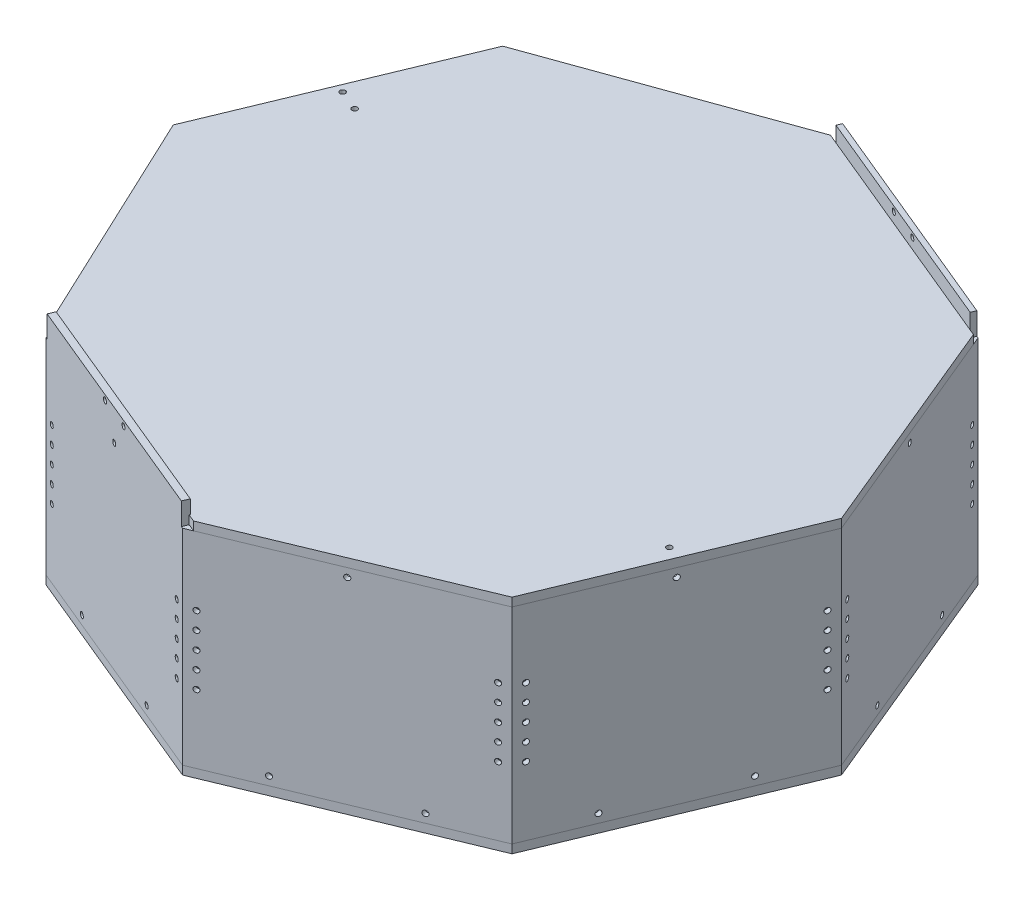
SolidWorks part; units mm, degrees
material "PMMA"
ref_plane "前视基准面" through (0, 0, 0) normal (0, 0, 1) x (1, 0, 0)
ref_plane "上视基准面" through (0, 0, 0) normal (0, 1, 0) x (1, 0, 0)
ref_plane "右视基准面" through (0, 0, 0) normal (1, 0, 0) x (0, 0, -1)
sketch "草图1" plane through (0, 0, 0) normal (0, 1, 0) x (1, 0, 0)
  line L0 (0, 0) -> (189.4186, 0) construction
  line L1 (189.4186, 0) -> (133.9392, 133.9392)
  line L2 (133.9392, 133.9392) -> (0, 189.4186)
  line L3 (0, 189.4186) -> (-133.9392, 133.9392)
  line L4 (-133.9392, 133.9392) -> (-189.4186, 0)
  line L5 (-189.4186, 0) -> (-133.9392, -133.9392)
  line L6 (-133.9392, -133.9392) -> (0, -189.4186)
  line L7 (0, -189.4186) -> (133.9392, -133.9392)
  line L8 (133.9392, -133.9392) -> (189.4186, 0)
  line L9 (0, -192.6658) -> (136.2353, -136.2353)
  line L10 (136.2353, -136.2353) -> (192.6658, 0)
  line L11 (192.6658, 0) -> (136.2353, 136.2353)
  line L12 (136.2353, 136.2353) -> (0, 192.6658)
  line L13 (0, 192.6658) -> (-136.2353, 136.2353)
  line L14 (-136.2353, 136.2353) -> (-192.6658, 0)
  line L15 (-192.6658, 0) -> (-136.2353, -136.2353)
  line L16 (-136.2353, -136.2353) -> (0, -192.6658)
  circle A2 centre (0, 0) radius 175 construction
  dimension "D1" = 3
  dimension "D3" = 350
extrude "凸台-拉伸1" add sketch "草图1" along normal blind 120
sketch "草图2" plane through (0, 0, 0) normal (0, -1, 0) x (1, 0, 0)
  line L10 (0, 192.6658) -> (-136.2353, 136.2353)
  line L11 (-136.2353, 136.2353) -> (-192.6658, 0)
  line L12 (-192.6658, 0) -> (-136.2353, -136.2353)
  line L13 (-136.2353, -136.2353) -> (0, -192.6658)
  line L14 (0, -192.6658) -> (136.2353, -136.2353)
  line L15 (136.2353, -136.2353) -> (192.6658, 0)
  line L16 (192.6658, 0) -> (136.2353, 136.2353)
  line L17 (136.2353, 136.2353) -> (0, 192.6658)
  line L18 (0, 192.6658) -> (-136.2353, 136.2353)
  line L19 (-136.2353, 136.2353) -> (-192.6658, 0)
  line L20 (-192.6658, 0) -> (-136.2353, -136.2353)
  line L21 (-136.2353, -136.2353) -> (0, -192.6658)
  line L22 (0, -192.6658) -> (136.2353, -136.2353)
  line L23 (136.2353, -136.2353) -> (192.6658, 0)
  line L24 (192.6658, 0) -> (136.2353, 136.2353)
  line L25 (136.2353, 136.2353) -> (0, 192.6658)
  dimension "D1" = 0
extrude "凸台-拉伸2" add sketch "草图2" along normal blind 5 separate body
sketch "草图3" plane through (0, -5, 0) normal (0, -1, 0) x (1, 0, 0)
  circle A0 centre (0, 0) radius 165 construction
  circle A1 centre (0, -165) radius 5.2
  circle A2 centre (-116.6726, -116.6726) radius 5.2
  circle A3 centre (-165, 0) radius 5.2
  circle A4 centre (-116.6726, 116.6726) radius 5.2
  circle A5 centre (0, 165) radius 5.2
  circle A6 centre (116.6726, 116.6726) radius 5.2
  circle A7 centre (165, 0) radius 5.2
  circle A8 centre (116.6726, -116.6726) radius 5.2
  circle A10 centre (0, 0) radius 22.5
  circle A11 centre (0, 0) radius 29 construction
  circle A12 centre (29, 0) radius 2.05
  circle A13 centre (-14.5, -25.1147) radius 2.05
  circle A14 centre (-14.5, 25.1147) radius 2.05
  dimension "D1" = 330
  dimension "D2" = 10.4
  dimension "D4" = 45
  dimension "D5" = 58
  dimension "D6" = 4.1
  dimension "D3" = 8
  dimension "D7" = 3
extrude "切除-拉伸1" cut sketch "草图3" against normal through all
sketch "草图6" plane through (0, -5, 0) normal (0, -1, 0) x (1, 0, 0)
  line L0 (0, 189.4186) -> (133.9392, 133.9392) construction
  line L1 (0, 189.4186) -> (133.9392, 133.9392) construction
  line L2 (66.9696, 161.6789) -> (0, 0) construction
  line L3 (-32.7204, 170.4534) -> (0, 0) construction
  line L4 (0, 0) -> (-97.392, 143.6656) construction
  line L5 (-97.392, 143.6656) -> (-32.7204, 170.4534) construction
  line L6 (-65.0562, 157.0595) -> (0, 0) construction
  line L7 (32.7204, 170.4534) -> (97.392, 143.6656) construction
  line L8 (65.0562, 157.0595) -> (0, 0) construction
  circle A11 centre (32.7204, 170.4534) radius 1.6
  circle A12 centre (97.392, 143.6656) radius 1.6
  circle A13 centre (143.6656, 97.392) radius 1.6
  circle A14 centre (170.4534, 32.7204) radius 1.6
  circle A15 centre (170.4534, -32.7204) radius 1.6
  circle A16 centre (143.6656, -97.392) radius 1.6
  circle A17 centre (97.392, -143.6656) radius 1.6
  circle A18 centre (32.7204, -170.4534) radius 1.6
  circle A19 centre (-32.7204, -170.4534) radius 1.6
  circle A20 centre (-97.392, -143.6656) radius 1.6
  circle A21 centre (-143.6656, -97.392) radius 1.6
  circle A22 centre (-170.4534, -32.7204) radius 1.6
  circle A23 centre (-170.4534, 32.7204) radius 1.6
  circle A24 centre (-143.6656, 97.392) radius 1.6
  circle A25 centre (-97.392, 143.6656) radius 1.6
  circle A26 centre (-32.7204, 170.4534) radius 1.6
  dimension "D1" = 3.2
  dimension "D2" = 35
  dimension "D3" = 5
  dimension "D4" = 170
extrude "切除-拉伸2" cut sketch "草图6" against normal through all
sketch "草图4" plane through (0, 120, 0) normal (0, 1, 0) x (1, 0, 0)
  line L0 (-133.9392, -133.9392) -> (0, -189.4186) construction
  line L1 (133.9392, 133.9392) -> (0, 189.4186) construction
  line L2 (-133.9392, -133.9392) -> (0, -189.4186) construction
  line L3 (133.9392, 133.9392) -> (0, 189.4186) construction
  line L4 (4.573, -190.7716) -> (-138.1295, -131.6623)
  line L5 (138.1295, 131.6623) -> (-4.573, 190.7716)
  line L6 (164.4506, -68.1177) -> (-164.4506, 68.1177) construction
  line L7 (0, 0) -> (-18.7005, -45.1469) construction
  line L8 (-136.2353, -136.2353) -> (0, -192.6658)
  line L9 (0, -192.6658) -> (136.2353, -136.2353)
  line L10 (136.2353, -136.2353) -> (192.6658, 0)
  line L11 (192.6658, 0) -> (136.2353, 136.2353)
  line L12 (136.2353, 136.2353) -> (0, 192.6658)
  line L13 (0, 192.6658) -> (-136.2353, 136.2353)
  line L14 (-136.2353, 136.2353) -> (-192.6658, 0)
  line L15 (-192.6658, 0) -> (-136.2353, -136.2353)
  line L17 (4.573, -190.7716) -> (136.2353, -136.2353)
  line L18 (136.2353, -136.2353) -> (192.6658, 0)
  line L19 (192.6658, 0) -> (138.1295, 131.6623)
  line L21 (-4.573, 190.7716) -> (-136.2353, 136.2353) construction
  line L22 (-136.2353, 136.2353) -> (-192.6658, 0) construction
  line L23 (-192.6658, 0) -> (-138.1295, -131.6623) construction
  line L24 (-133.9392, 133.9392) -> (-189.4186, 0) construction
  line L25 (-136.2353, 136.2353) -> (-145.4741, 140.0621) construction
  line L26 (-145.4741, 140.0621) -> (-201.9046, 3.8268)
  line L27 (-201.9046, 3.8268) -> (-192.6658, 0) construction
  line L28 (-4.573, 190.7716) -> (-145.4741, 140.0621)
  line L29 (-201.9046, 3.8268) -> (-138.1295, -131.6623)
  circle A0 centre (157.0595, -65.0562) radius 1.6
  circle A1 centre (-157.0595, 65.0562) radius 1.6
  circle A2 centre (-169.07, 70.0311) radius 1.6
  dimension "D4" = 3.2
  dimension "D2" = 0.5
  dimension "D3" = 0.5
  dimension "D5" = 5
  dimension "D6" = 10
  dimension "D7" = 5
  dimension "D1" = 0
extrude "凸台-拉伸3" add sketch "草图4" along normal blind 5 separate body
sketch "草图8" plane through (-68.1177, 0, 164.4506) normal (-0.3827, 0, 0.9239) x (0.9239, 0, 0.3827)
  line L1 (-72.4874, 120) -> (72.4874, 120)
  line L2 (-72.4874, 120) -> (-72.4874, 133)
  line L3 (-72.4874, 133) -> (72.4874, 133)
  line L4 (72.4874, 120) -> (72.4874, 133)
  line L5 (0, 133) -> (0, 120) construction
  line L6 (-10, 130) -> (10, 130) construction
  circle A1 centre (-10, 130) radius 1.6
  circle A2 centre (10, 130) radius 1.6
  dimension "D2" = 3.2
  dimension "D1" = 13
  dimension "D3" = 20
  dimension "D4" = 3
extrude "凸台-拉伸4" add sketch "草图8" against normal blind 4
extrude "凸台-拉伸6" add sketch "草图8<2>" against normal up to surface (356 mm away) from surface up to face at (68.1177, 60, -164.4506) starting at face at (66.9696, 60, -161.6789)
sketch "草图8<2>" plane through (-68.1177, 0, 164.4506) normal (-0.3827, 0, 0.9239) x (0.9239, 0, 0.3827) same geometry as "草图8"
sketch "草图9" plane through (-164.4506, 0, -68.1177) normal (-0.9239, 0, -0.3827) x (-0.3827, 0, 0.9239)
  line L0 (-35, 5) -> (35, 5) construction
  line L1 (0, 5) -> (0, 0) construction
  line L2 (73.73, 0) -> (-73.73, 0) construction
  line L3 (-73.73, 60) -> (73.73, 60) construction
  line L4 (-73.73, 120) -> (-73.73, 0) construction
  line L5 (73.73, 120) -> (73.73, 0) construction
  line L6 (-73.73, 120) -> (73.73, 120) construction
  line L7 (-67.4874, 80) -> (-67.4874, 40) construction
  line L8 (67.4874, 70) -> (67.4874, 50) construction
  circle A0 centre (-35, 5) radius 1.6
  circle A1 centre (35, 5) radius 1.6
  circle A4 centre (0, 115) radius 1.6
  circle A5 centre (-67.4874, 80) radius 1.6
  circle A6 centre (-67.4874, 40) radius 1.6
  circle A9 centre (67.4874, 70) radius 1.6
  circle A10 centre (67.4874, 50) radius 1.6
  circle A11 centre (-67.4874, 60) radius 1.6
  dimension "D2" = 3.2
  dimension "D4" = 3.2
  dimension "D6" = 3.2
  dimension "D1" = 5
  dimension "D3" = 70
  dimension "D5" = 40
  dimension "D7" = 5
  dimension "D8" = 5
  dimension "D9" = 5
  dimension "D10" = 20
extrude "切除-拉伸5" cut sketch "草图9" against normal through all both and the other way through all
pattern_circular "阵列(圆周)2" count 8 over 360 about axis through (0, 0, 0) along (0, -1, 0) of "切除-拉伸5"
sketch "草图10" plane through (0, 0, 0) normal (0, 1, 0) x (1, 0, 0)
  line L0 (133.9392, 133.9392) -> (123.9148, 138.0914)
  line L1 (133.9392, 133.9392) -> (0, 189.4186) construction
  line L2 (121.7352, 134.8295) -> (134.8295, 121.7352)
  line L3 (189.4186, 0) -> (133.9392, 133.9392) construction
  line L4 (138.0914, 123.9148) -> (133.9392, 133.9392)
  arc A0 (134.8295, 121.7352) -> (138.0914, 123.9148) centre (136.2437, 123.1494) ccw
  arc A1 (123.9148, 138.0914) -> (121.7352, 134.8295) centre (123.1494, 136.2437) ccw
  point P10 (141.9392, 114.6255)
  point P13 (114.6255, 141.9392)
  dimension "D2" = 2
  dimension "D1" = 8
extrude "凸台-拉伸5" add sketch "草图10" along normal blind 60 from offset 30 separate body
sketch "草图11" plane through (66.9696, 0, -161.6789) normal (0.3827, 0, -0.9239) x (-0.9239, 0, -0.3827)
  circle A10 centre (-67.4874, 80) radius 1.2
  circle A11 centre (-67.4874, 70) radius 1.2
  circle A12 centre (-67.4874, 60) radius 1.2
  circle A13 centre (-67.4874, 50) radius 1.2
  circle A14 centre (-67.4874, 40) radius 1.2
  dimension "D1" = 2.4
extrude "切除-拉伸6" cut sketch "草图11" against normal up to surface (6.091 mm away) up to face at (128.2823, 60, -128.2823)
sketch "草图13" plane through (161.6789, 0, -66.9696) normal (0.9239, 0, -0.3827) x (-0.3827, 0, -0.9239)
  circle A0 centre (67.4874, 80) radius 1.2
  circle A1 centre (67.4874, 70) radius 1.2
  circle A2 centre (67.4874, 60) radius 1.2
  circle A3 centre (67.4874, 50) radius 1.2
  circle A4 centre (67.4874, 40) radius 1.2
  dimension "D1" = 2.4
extrude "切除-拉伸7" cut sketch "草图13" against normal up to surface (7.0851 mm away) up to face at (125.8802, 80, -130.6845)
pattern_circular "阵列(圆周)3" count 8 over 360 about axis through (0, 0, 0) along (0, -1, 0) of bodies 122
sketch "草图14" plane through (0, -5, 0) normal (0, -1, 0) x (1, 0, 0)
  line L1 (50, -50) -> (-50, -50) construction
  line L2 (50, -50) -> (50, 50) construction
  line L3 (50, 50) -> (-50, 50) construction
  line L4 (-50, -50) -> (-50, 50) construction
  line L5 (50, -50) -> (-50, 50) construction
  line L6 (50, 50) -> (-50, -50) construction
  line L14 (54, -54) -> (54, 54) construction
  line L15 (54, 54) -> (-54, 54) construction
  line L16 (-54, -54) -> (-54, 54) construction
  line L17 (54, -54) -> (-54, -54) construction
  line L19 (-50, -50) -> (-54, -50)
  line L20 (-50, -50) -> (-50, 50)
  line L21 (-50, 50) -> (-54, 50)
  line L22 (-54, -50) -> (-54, 50)
  point P0 (0, 0)
  dimension "D1" = 100
  dimension "D2" = 4
extrude "凸台-拉伸7" add sketch "草图14" along normal blind 55 separate body
sketch "草图15" plane through (0, -60, 0) normal (0, -1, 0) x (1, 0, 0)
  line L0 (-50, 50) -> (-54, 50) construction
  line L1 (-50, -50) -> (50, -50)
  line L2 (-50, -50) -> (-50, 50)
  line L3 (-50, 50) -> (50, 50)
  line L4 (50, -50) -> (50, 50)
  line L5 (-50, -50) -> (-50, 50) construction
  line L6 (-54, -50) -> (-50, -50) construction
  point P9 (-50, -47.3887)
  dimension "D1" = 100
extrude "凸台-拉伸8" add sketch "草图15" along normal blind 3 separate body
sketch "草图16" plane through (0, -63, 0) normal (0, -1, 0) x (1, 0, 0)
  line L0 (50, 0) -> (-50, 0) construction
  line L1 (50, -50) -> (50, 50) construction
  line L2 (-50, 50) -> (-50, -50) construction
  circle A0 centre (0, 0) radius 3.05
  circle A1 centre (0, 0) radius 12.5 construction
  circle A2 centre (0, -12.5) radius 1.35
  circle A3 centre (-10.8253, 6.25) radius 1.35
  circle A4 centre (10.8253, 6.25) radius 1.35
  point P12 (10.826, 6.2489)
  point P13 (-10.7914, 6.3084)
  dimension "D1" = 6.1
  dimension "D2" = 25
  dimension "D3" = 2.7
  dimension "D4" = 3
extrude "切除-拉伸8" cut sketch "草图16" against normal up to next (3 mm away)
sketch "草图17" plane through (0, -5, 0) normal (0, -1, 0) x (1, 0, 0)
  line L0 (-59, -49.5402) -> (-59, 46.5588) construction
  line L1 (-50, -50) -> (-50, 50) construction
  line L2 (-50, 50) -> (-54, 50) construction
  line L3 (-54, -50) -> (-50, -50) construction
  line L4 (-54, 50) -> (-54, -50) construction
  circle A0 centre (-59, -30) radius 1.6
  circle A1 centre (-59, 30) radius 1.6
  circle A2 centre (-30, 59) radius 1.6
  circle A3 centre (30, 59) radius 1.6
  circle A4 centre (59, 30) radius 1.6
  circle A5 centre (59, -30) radius 1.6
  circle A6 centre (30, -59) radius 1.6
  circle A7 centre (-30, -59) radius 1.6
  circle A8 centre (0, 0) radius 66.1891 construction
  point P16 (-29.8667, -59.0676)
  point P29 (30.0482, -58.9755)
  dimension "D2" = 3.2
  dimension "D1" = 5
  dimension "D3" = 20
  dimension "D4" = 20
  dimension "D5" = 4
extrude "切除-拉伸9" cut sketch "草图17" against normal up to next (5 mm away)
sketch "草图18" plane through (-54, 0, 0) normal (-1, 0, 0) x (0, 0, 1)
  line L0 (-50, -10) -> (50, -10) construction
  line L1 (-50, -60) -> (-50, -5) construction
  line L2 (50, -60) -> (50, -5) construction
  line L3 (50, -5) -> (-50, -5) construction
  line L4 (-50, -32.5) -> (-36.0118, -32.5) construction
  circle A0 centre (-30, -10) radius 1.6
  circle A1 centre (30, -10) radius 1.6
  circle A2 centre (30, -55) radius 1.6
  circle A3 centre (-30, -55) radius 1.6
  dimension "D1" = 3.2
  dimension "D2" = 5
  dimension "D3" = 20
  dimension "D4" = 20
extrude "切除-拉伸10" cut sketch "草图18" against normal up to next (4 mm away)
sketch "草图19" plane through (0, -63, 0) normal (0, -1, 0) x (1, 0, 0)
  line L0 (-45, -50) -> (-45, 50) construction
  line L1 (-50, -50) -> (50, -50) construction
  line L2 (50, 50) -> (-50, 50) construction
  line L3 (-50, 50) -> (-50, -50) construction
  circle A0 centre (-45, -30) radius 1.6
  circle A1 centre (-45, 30) radius 1.6
  dimension "D1" = 3.2
  dimension "D2" = 20
  dimension "D3" = 20
  dimension "D4" = 5
extrude "切除-拉伸11" cut sketch "草图19" against normal up to next (3 mm away)
